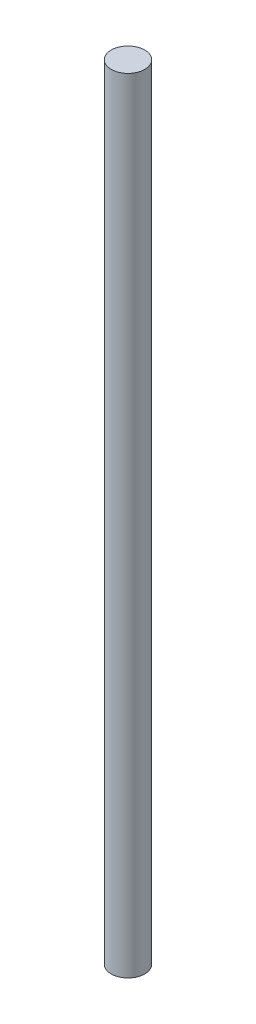
SolidWorks part; units mm, degrees
ref_plane "Plan de face" through (0, 0, 0) normal (0, 0, 1) x (1, 0, 0)
ref_plane "Plan de dessus" through (0, 0, 0) normal (0, 1, 0) x (1, 0, 0)
ref_plane "Plan de droite" through (0, 0, 0) normal (1, 0, 0) x (0, 0, -1)
sketch "Sketch1" plane through (0, 0, 0) normal (0, 1, 0) x (1, 0, 0)
  circle A0 centre (0, 0) radius 1.5
extrude "Boss-Extrude1" add sketch "Sketch1" along normal blind 70
